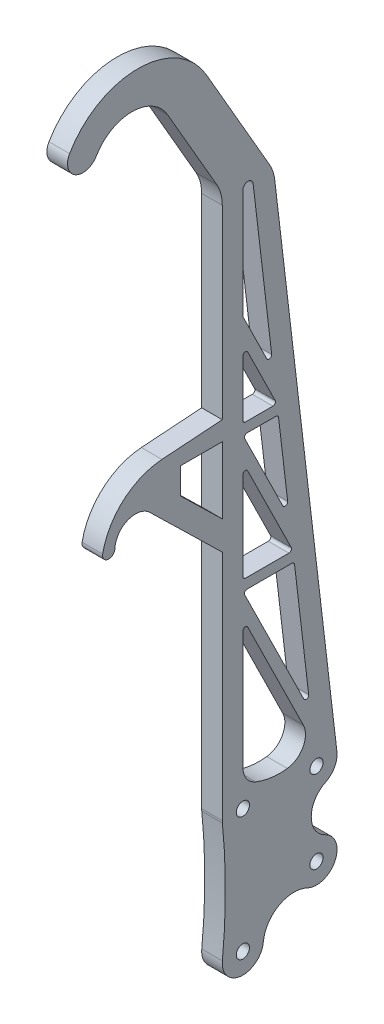
SolidWorks part; units mm, degrees
ref_plane "Front Plane" through (0, 0, 0) normal (0, 0, 1) x (1, 0, 0)
ref_plane "Top Plane" through (0, 0, 0) normal (0, 1, 0) x (1, 0, 0)
ref_plane "Right Plane" through (0, 0, 0) normal (1, 0, 0) x (0, 0, -1)
sketch "Sketch1" plane through (0, 0, 0) normal (1, 0, 0) x (0, 0, -1)
  line L1 (11.35, 19.05) -> (11.35, -6.35) construction
  line L2 (-11.35, -19.05) -> (-11.35, 19.05) construction
  line L3 (11.35, 0) -> (-11.35, 0) construction
  line L4 (-6.35, 19.05) -> (6.35, 19.05) construction
  line L5 (-17.7, 19.05) -> (-17.7, 183.3563)
  line L6 (8.5879, -12.0678) -> (-3.6653, -6.1486) construction
  line L7 (17.6561, 19.7951) -> (-1.825, 184.6629)
  line L8 (-11.35, 25.4) -> (-11.35, 69.85)
  line L9 (-56.5215, 215.9) -> (-71.6445, 189.7062) construction
  line L10 (-60.6459, 170.6563) -> (-30.4, 170.6563) construction
  line L11 (-19.4015, 189.7062) -> (-34.5244, 215.9)
  line L12 (-45.523, 209.55) -> (-60.6459, 183.3562) construction
  line L13 (-60.6459, 183.3562) -> (-30.4, 183.3562) construction
  line L14 (-30.4, 183.3562) -> (-45.523, 209.55) construction
  line L15 (-22.6094, 220.6625) -> (-1.825, 184.6629)
  line L16 (-1.825, 184.6629) -> (-12.8235, 178.3129) construction
  line L17 (-56.5215, 215.9) -> (-64.7704, 220.6625) construction
  line L18 (14.1121, -0.6322) -> (6.2486, 3.1664) construction
  line L19 (-11.35, 69.85) -> (10.6049, 25.3561)
  line L20 (10.6049, 25.3561) -> (-0.8043, 121.9108) construction
  line L21 (8.5879, 24.7678) -> (0.6662, 20.9411) construction
  line L22 (14.1121, 13.3322) -> (6.5563, 9.6822) construction
  line L23 (9.4901, 34.7905) -> (-11.35, 77.0252)
  line L24 (-11.35, 77.0252) -> (4.4995, 77.0252)
  line L25 (4.4995, 77.0252) -> (9.4901, 34.7905)
  line L26 (4.1244, 80.2002) -> (-11.35, 80.2002)
  line L27 (-11.35, 80.2002) -> (-11.35, 111.5606)
  line L28 (-11.35, 111.5606) -> (4.1244, 80.2002)
  line L29 (3.0096, 89.6346) -> (-11.35, 118.7358)
  line L30 (-11.35, 118.7358) -> (-0.4291, 118.7358)
  line L31 (-0.4291, 118.7358) -> (3.0096, 89.6346)
  line L32 (-0.8043, 121.9108) -> (-11.35, 121.9108)
  line L33 (-11.35, 121.9108) -> (-11.35, 143.2829)
  line L34 (-8.186, 184.3819) -> (-1.919, 131.3452)
  line L35 (-11.35, 69.85) -> (-8.5028, 71.2549) construction
  line L36 (-11.35, 77.0252) -> (-11.35, 80.2002) construction
  line L37 (-11.35, 111.5606) -> (-8.5028, 112.9656) construction
  line L38 (-11.35, 118.7358) -> (-11.35, 121.9108) construction
  line L39 (-0.8043, 121.9108) -> (-11.35, 143.2829)
  line L40 (-1.919, 131.3452) -> (-11.35, 150.4581)
  line L41 (-11.35, 143.2829) -> (-8.5028, 144.6878) construction
  line L42 (-1.919, 131.3452) -> (-1.3257, 126.3235) construction
  line L43 (-11.35, 150.4581) -> (-11.35, 184.1956)
  line L44 (-17.6679, -18.4122) -> (-15.1883, 6.15) construction
  line L45 (-5.0321, -19.6878) -> (-3.6653, -6.1486) construction
  circle A0 centre (-11.35, 19.05) radius 5 construction
  circle A1 centre (11.35, 19.05) radius 5 construction
  arc A2 (-17.6679, -18.4122) -> (-5.0321, -19.6878) centre (-11.35, -19.05) ccw
  arc A3 (8.5879, -12.0678) -> (14.1121, -0.6322) centre (11.35, -6.35) ccw
  arc A4 (14.1121, 13.3322) -> (17.6561, 19.7951) centre (11.35, 19.05) ccw
  arc A5 (14.1121, 13.3322) -> (14.1121, -0.6322) centre (17.485, 6.35) ccw
  arc A7 (-34.5244, 215.9) -> (-56.5215, 215.9) centre (-45.523, 209.55) ccw
  arc A8 (-71.6445, 189.7062) -> (-60.6459, 170.6563) centre (-60.6459, 183.3562) ccw construction
  arc A9 (-30.4, 170.6563) -> (-19.4015, 189.7062) centre (-30.4, 183.3562) ccw construction
  circle A10 centre (-45.523, 192.0875) radius 8.7312 construction
  arc A11 (-17.7, 183.3563) -> (-19.4015, 189.7062) centre (-30.4, 183.3563) ccw
  arc A12 (-56.5215, 215.9) -> (-64.7704, 220.6625) centre (-60.6459, 218.2813) cw
  arc A13 (-64.7704, 220.6625) -> (-22.6094, 220.6625) centre (-43.6899, 208.4917) cw
  arc A14 (-5.0321, -19.6878) -> (8.5879, -12.0678) centre (4.4447, -20.6445) cw
  arc A15 (-11.35, 25.4) -> (-8.5879, 24.7678) centre (-11.35, 19.05) cw
  arc A17 (10.6049, 25.3561) -> (8.5879, 24.7678) centre (11.35, 19.05) ccw
  arc A18 (8.5879, 24.7678) -> (-8.5879, 24.7678) centre (0, 42.5454) cw
  arc A19 (-11.35, 184.1956) -> (-8.186, 184.3819) centre (-9.7625, 184.1956) cw
  arc A20 (-17.7, 19.05) -> (-17.6679, 18.4122) centre (-11.35, 19.05) ccw
  arc A21 (-17.6679, -18.4122) -> (-17.6679, 18.4122) centre (-200.0545, 0) ccw
  point P11 (0, 0)
  point P47 (-11.35, 0)
  point P48 (-45.523, 222.25)
  dimension "D3" = 12.7
  dimension "D4" = 10
  dimension "D5" = 6.35
  dimension "D6" = 15.875
  dimension "D7" = 12.7
  dimension "D9" = 12.7
  dimension "D10" = 4.7625
  dimension "D12" = 6.35
  dimension "D14" = 3.175
  dimension "D15" = 1.5875
  dimension "D17" = 9.525
  dimension "D1" = 25.4
  dimension "D2" = 38.1
  dimension "D8" = 38.8937
  dimension "D11" = 222.25
  dimension "D13" = 6.35
  dimension "D16" = 44.45
extrude "Boss-Extrude1" add sketch "Sketch1" along normal mid plane 6.35
sketch "Sketch2" plane through (3.175, 0, 0) normal (1, 0, 0) x (0, 0, -1)
  line L0 (-11.35, -19.05) -> (-11.35, 19.05) construction
  circle A0 centre (11.35, -6.35) radius 2.032
  circle A1 centre (11.35, 19.05) radius 2.032
  circle A2 centre (-11.35, 19.05) radius 2.032
  circle A3 centre (-11.35, -19.05) radius 2.032
  dimension "D1" = 4.064
extrude "Cut-Extrude1" cut sketch "Sketch2" against normal through all
fillet "Fillet1" radius 12.7 1 edges at (0, 184.6629, 1.825)
fillet "Fillet2" radius 0.7937 15 edges at (0, 121.9108, 11.35) (0, 118.7358, 11.35) (0, 118.7358, 0.4291) (0, 89.6346, -3.0096) (0, 111.5606, 11.35) (0, 80.2002, 11.35) (0, 80.2002, -4.1244) (0, 69.85, 11.35) (0, 77.0252, 11.35) (0, 77.0252, -4.4995) (0, 34.7905, -9.4901) (0, 150.4581, 11.35) (0, 121.9108, 0.8043) (0, 143.2829, 11.35) (0, 131.3452, 1.919)
fillet "Fillet3" radius 6.35 2 edges at (0, 25.4, 11.35) (0, 25.3561, -10.6049)
sketch "Sketch3" plane through (3.175, 0, 0) normal (1, 0, 0) x (0, 0, -1)
  line L1 (-17.7, 183.3563) -> (-17.7, 19.05) construction
  line L2 (-17.7, 126.0915) -> (-17.7, 90.742)
  line L3 (-40.0175, 112.4971) -> (-17.7, 90.742)
  line L4 (-17.7, 126.0915) -> (-36.2948, 124.792)
  arc A0 (-40.0175, 112.4971) -> (-50.7948, 108.2077) centre (-44.45, 107.95) ccw
  arc A1 (-36.2948, 124.792) -> (-54.5676, 108.6515) centre (-34.8973, 104.7962) ccw
  arc A2 (-54.5676, 108.6515) -> (-50.7948, 108.2077) centre (-52.6982, 108.2851) ccw
  point P3 (-43.798, 111.2113)
  point P11 (-44.6102, 113.0256)
  point P12 (-35.9783, 117.7343)
  point P14 (-41.135, 115.6268)
  point P15 (-17.7, 90.742)
  point P17 (-43.0222, 115.887)
  point P18 (-46.3482, 108.2077)
  point P19 (-17.7, 126.0915)
  dimension "D1" = 6.35
  dimension "D2" = 107.95
  dimension "D3" = 44.45
extrude "Boss-Extrude2" add sketch "Sketch3" against normal up to surface (6.35 mm away) up to face at (-3.175, -19.05, 9.318)
sketch "Sketch4" plane through (3.175, 0, 0) normal (1, 0, 0) x (0, 0, -1)
  line L0 (-17.7, 99.6098) -> (-30.5107, 112.0977)
  line L1 (-30.5107, 112.0977) -> (-30.5107, 120.2194)
  line L2 (-30.5107, 120.2194) -> (-17.7, 120.2194)
  line L3 (-17.7, 120.2194) -> (-17.7, 99.6098)
  line L4 (-40.0175, 112.4971) -> (-17.7, 90.742) construction
  line L5 (-17.7, 90.742) -> (-17.7, 19.05) construction
  dimension "D1" = 6.35
extrude "Cut-Extrude2" cut sketch "Sketch4" against normal through all
